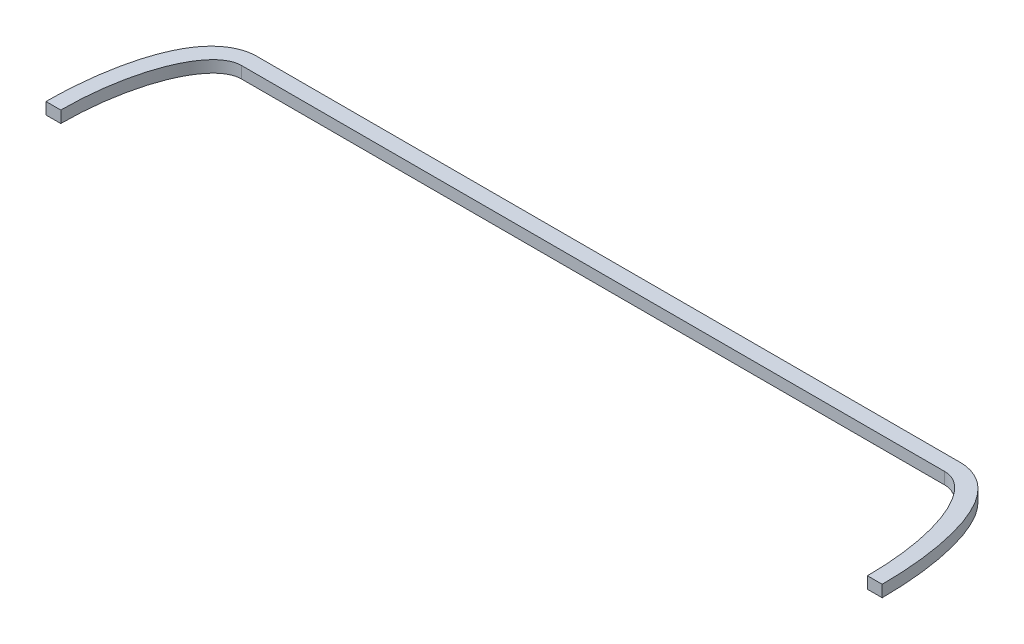
SolidWorks part; units mm, degrees
ref_plane "Front Plane" through (0, 0, 0) normal (0, 0, 1) x (1, 0, 0)
ref_plane "Top Plane" through (0, 0, 0) normal (0, 1, 0) x (1, 0, 0)
ref_plane "Right Plane" through (0, 0, 0) normal (1, 0, 0) x (0, 0, -1)
sketch "Sketch5" plane through (0, 0, 0) normal (0, 1, 0) x (1, 0, 0)
  line L0 (45, 15) -> (-45, -15) construction
  line L1 (-45, 15) -> (45, 15)
  line L2 (-45, 15) -> (-45, -15) construction
  line L3 (-45, -15) -> (45, -15)
  line L4 (45, 15) -> (45, -15) construction
  line L5 (-45, 15) -> (45, -15) construction
  line L6 (0, 15) -> (0, -15) construction
  ellipse E0 centre (-45, 0) end of major axis (-45, 15) minor radius 5 (-45, 15) -> (-45, -15) ccw
  ellipse E1 centre (45, 0) end of major axis (45, -15) minor radius 5 (45, 15) -> (45, -15) cw
  point P0 (0, 0)
  point P5 (0, 0)
  dimension "D1" = 30
  dimension "D2" = 90
  dimension "D3" = 5
extrude "Boss-Extrude1" add sketch "Sketch5" along normal blind 1.5
shell "Shell3" thickness 3.5 removed face at (0, 0, 0) removed face at (0, 1.5, 0) outward yes
sketch "Sketch6" plane through (0, 0, 0) normal (0, 1, 0) x (1, 0, 0)
  line L0 (45, 16.5) -> (-45, -16.5) construction
  line L1 (-45, 16.5) -> (45, 16.5)
  line L2 (-45, 16.5) -> (-45, -16.5) construction
  line L3 (-45, -16.5) -> (45, -16.5)
  line L4 (45, 16.5) -> (45, -16.5) construction
  line L5 (-45, 16.5) -> (45, -16.5) construction
  line L6 (0, 16.5) -> (0, -16.5) construction
  ellipse E0 centre (-45, 0) end of major axis (-45, -16.5) minor radius 6.6112 (-45, 16.5) -> (-45, -16.5) ccw
  ellipse E1 centre (45, 0) end of major axis (45, -16.5) minor radius 6.6112 (45, 16.5) -> (45, -16.5) cw
  point P0 (0, 0)
  point P5 (0, 0)
  dimension "D1" = 33
  dimension "D2" = 90
extrude "Cut-Extrude2" cut sketch "Sketch6" along normal through all
sketch "Sketch7" plane through (0, 0, 0) normal (0, 1, 0) x (1, 0, 0)
  line L1 (-57.7028, 0) -> (61.2936, 0)
  line L2 (-57.7028, 0) -> (-57.7028, -25.3218)
  line L3 (-57.7028, -25.3218) -> (61.2936, -25.3218)
  line L4 (61.2936, 0) -> (61.2936, -25.3218)
extrude "Cut-Extrude4" cut sketch "Sketch7" along normal through all
